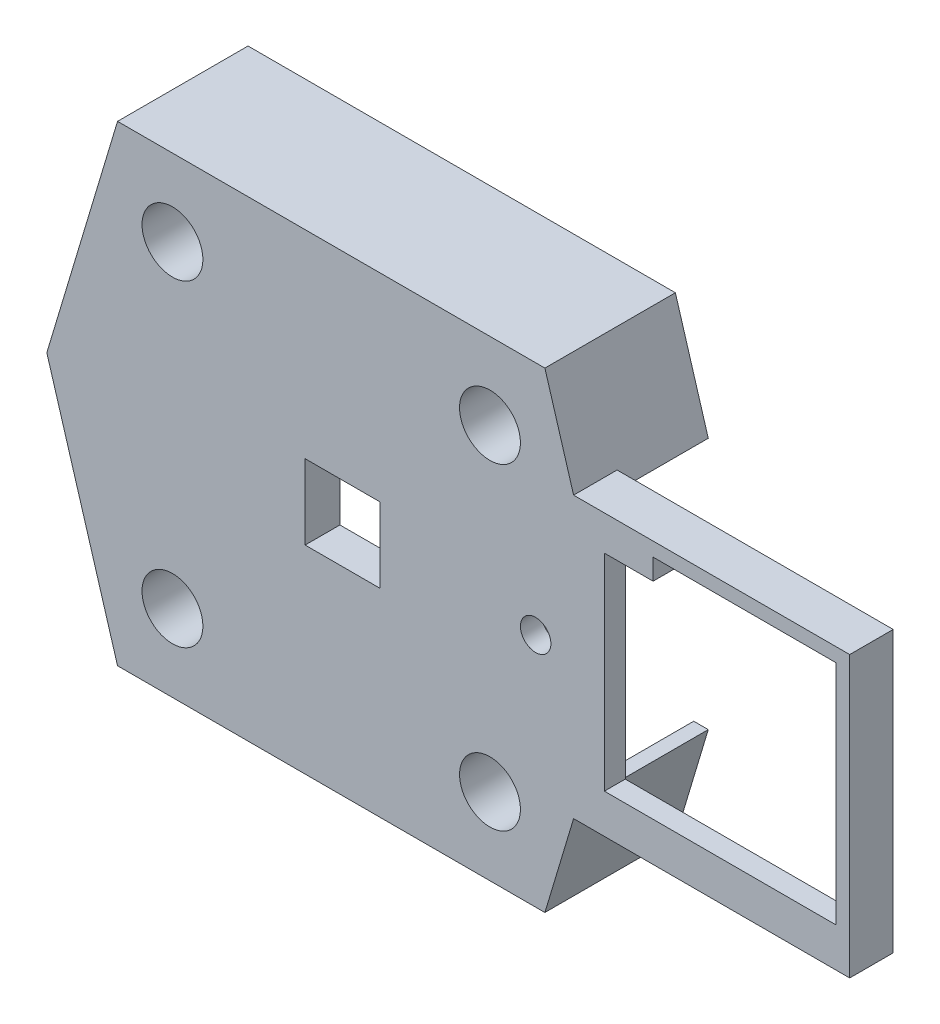
SolidWorks part; units mm, degrees
ref_plane "Front Plane" through (0, 0, 0) normal (0, 0, 1) x (1, 0, 0)
ref_plane "Top Plane" through (0, 0, 0) normal (0, 1, 0) x (1, 0, 0)
ref_plane "Right Plane" through (0, 0, 0) normal (1, 0, 0) x (0, 0, -1)
sketch "Sketch2" plane through (0, 0, 12) normal (0, 0, 1) x (1, 0, 0)
  line L10 (-24.5625, 27.1) -> (-32.6925, 0)
  line L11 (-32.6925, 0) -> (-24.5625, -27.1)
  line L12 (-24.5625, -27.1) -> (24.5625, -27.1)
  line L13 (24.5625, -27.1) -> (32.6925, 0)
  line L14 (32.6925, 0) -> (24.5625, 27.1)
  line L15 (24.5625, 27.1) -> (-24.5625, 27.1)
  line L16 (-23.372, 25.5) -> (-31.022, 0)
  line L17 (-31.022, 0) -> (-23.372, -25.5)
  line L18 (-23.372, -25.5) -> (23.372, -25.5)
  line L19 (23.372, -25.5) -> (31.022, 0)
  line L20 (31.022, 0) -> (23.372, 25.5)
  line L21 (23.372, 25.5) -> (-23.372, 25.5)
  line L22 (-23.372, 25.5) -> (-31.022, 0)
  line L23 (-31.022, 0) -> (-23.372, -25.5)
  line L24 (-23.372, -25.5) -> (23.372, -25.5)
  line L25 (23.372, -25.5) -> (31.022, 0)
  line L26 (31.022, 0) -> (23.372, 25.5)
  line L27 (23.372, 25.5) -> (-23.372, 25.5)
  dimension "D1" = 0.5
  dimension "D2" = 1.6
extrude "Boss-Extrude1" add sketch "Sketch2" along normal blind 10 and the other way blind 5
sketch "Sketch3" plane through (0, 0, 22) normal (0, 0, 1) x (1, 0, 0)
  line L0 (29.5, 16.1) -> (59.6, 16.1)
  line L1 (59.6, 16.1) -> (59.6, -16.1)
  line L2 (59.6, -16.1) -> (29.5, -16.1)
  line L3 (29.5, 16.1) -> (27.8625, 16.1)
  line L4 (27.8625, 16.1) -> (28.3425, 14.5)
  line L5 (29.5, -16.1) -> (27.8625, -16.1)
  line L6 (27.8625, -16.1) -> (28.3425, -14.5)
  line L12 (29.5, 14.5) -> (28.3425, 14.5)
  line L13 (32.6925, 0) -> (24.5625, 27.1) construction
  line L14 (29.5, -14.5) -> (28.3425, -14.5)
  line L15 (58, -14.5) -> (29.5, -14.5)
  line L16 (58, 14.5) -> (58, -14.5)
  line L17 (29.5, 14.5) -> (58, 14.5)
  line L18 (58, -14.5) -> (29.5, -14.5)
  line L19 (58, 14.5) -> (58, -14.5)
  line L20 (29.5, 14.5) -> (58, 14.5)
  line L21 (24.5625, -27.1) -> (32.6925, 0) construction
  dimension "D1" = 0.5
  dimension "D2" = 1.6
extrude "Boss-Extrude2" add sketch "Sketch3" against normal blind 5
sketch "Sketch4" plane through (0, 0, 7) normal (0, 0, -1) x (-1, 0, 0)
  line L0 (-28.3425, 14.5) -> (-26.672, 14.5)
  line L1 (-31.022, 0) -> (-23.372, 25.5) construction
  line L2 (-28.3425, -14.5) -> (-26.672, -14.5)
  line L3 (-23.372, -25.5) -> (-31.022, 0) construction
  line L6 (24.5625, 27.1) -> (-24.5625, 27.1)
  line L7 (-24.5625, 27.1) -> (-32.6925, 0)
  line L8 (-32.6925, 0) -> (-24.5625, -27.1)
  line L9 (-24.5625, -27.1) -> (24.5625, -27.1)
  line L10 (24.5625, -27.1) -> (32.6925, 0)
  line L11 (32.6925, 0) -> (24.5625, 27.1)
  line L12 (24.5625, 27.1) -> (-24.5625, 27.1)
  line L13 (-24.5625, 27.1) -> (-32.6925, 0)
  line L14 (-32.6925, 0) -> (-24.5625, -27.1)
  line L15 (-24.5625, -27.1) -> (24.5625, -27.1)
  line L16 (24.5625, -27.1) -> (32.6925, 0)
  line L17 (32.6925, 0) -> (24.5625, 27.1)
  line M7 (-31.022, 0) -> (-23.372, 25.5)
  line M12 (-23.372, -25.5) -> (-31.022, 0)
  line M14 (-24.5625, 27.1) -> (-32.6925, 0)
  line M15 (-32.6925, 0) -> (-24.5625, -27.1)
  dimension "D1" = 0
extrude "Cut-Extrude1" cut sketch "Sketch4" against normal through all contours L2 L0 M15 M12 M7 M14 region at (27.5072, 14.2038, 7)
sketch "Sketch5" plane through (0, 0, 22) normal (0, 0, 1) x (1, 0, 0)
  line L0 (-2.5, 3.8) -> (-2.5, -3.8) construction
  line L1 (-2.5, -3.8) -> (29.5, -3.8) construction
  line L2 (29.5, -3.8) -> (29.5, -14) construction
  line L3 (29.5, -14) -> (57.5, -14) construction
  line L4 (57.5, -14) -> (57.5, 14) construction
  line L5 (57.5, 14) -> (29.5, 14) construction
  line L6 (29.5, 14) -> (29.5, 3.8) construction
  line L7 (29.5, 3.8) -> (-2.5, 3.8) construction
  line L8 (24.5625, -27.1) -> (27.8625, -16.1) construction
  line L9 (27.8625, -16.1) -> (59.6, -16.1) construction
  line L10 (59.6, -16.1) -> (59.6, 16.1) construction
  line L11 (59.6, 16.1) -> (27.8625, 16.1) construction
  line L12 (27.8625, 16.1) -> (24.5625, 27.1) construction
  line L13 (24.5625, 27.1) -> (-24.5625, 27.1) construction
  line L14 (-24.5625, 27.1) -> (-32.6925, 0) construction
  line L15 (-32.6925, 0) -> (-24.5625, -27.1) construction
  line L16 (-24.5625, -27.1) -> (24.5625, -27.1) construction
  line L17 (-2.5, 3.8) -> (-2.5, -3.8)
  line L18 (-2.5, -3.8) -> (29.5, -3.8)
  line L19 (29.5, -3.8) -> (29.5, -14)
  line L20 (29.5, -14) -> (57.5, -14)
  line L21 (57.5, -14) -> (57.5, 14)
  line L22 (57.5, 14) -> (29.5, 14)
  line L23 (29.5, 14) -> (29.5, 3.8)
  line L24 (29.5, 3.8) -> (-2.5, 3.8)
  line L25 (24.5625, -27.1) -> (27.8625, -16.1)
  line L26 (27.8625, -16.1) -> (59.6, -16.1)
  line L27 (59.6, -16.1) -> (59.6, 16.1)
  line L28 (59.6, 16.1) -> (27.8625, 16.1)
  line L29 (27.8625, 16.1) -> (24.5625, 27.1)
  line L30 (24.5625, 27.1) -> (-24.5625, 27.1)
  line L31 (-24.5625, 27.1) -> (-32.6925, 0)
  line L32 (-32.6925, 0) -> (-24.5625, -27.1)
  line L33 (-24.5625, -27.1) -> (24.5625, -27.1)
  line L34 (29, 14) -> (29, 4.3)
  line L35 (29, 4.3) -> (-3, 4.3)
  line L36 (-3, 4.3) -> (-3, -4.3)
  line L37 (-3, -4.3) -> (29, -4.3)
  line L38 (29, -4.3) -> (29, -14)
  line L39 (29, 14) -> (29, 14.5)
  line L40 (26.672, 14.5) -> (58, 14.5) construction
  line L41 (29, -14) -> (29, -14.5)
  line L42 (58, -14.5) -> (26.672, -14.5) construction
  line L43 (27.4, 14) -> (27.4, 14.5)
  line L44 (27.4, 14) -> (27.4, 5.9)
  line L45 (27.4, 5.9) -> (-4.6, 5.9)
  line L46 (-4.6, 5.9) -> (-4.6, -5.9)
  line L47 (-4.6, -5.9) -> (27.4, -5.9)
  line L48 (27.4, -5.9) -> (27.4, -14)
  line L49 (27.4, -14) -> (27.4, -14.5)
  circle A0 centre (18.25, -18.25) radius 3.5 construction
  circle A1 centre (-18.25, -18.25) radius 3.5 construction
  circle A2 centre (-18.25, 18.25) radius 3.5 construction
  circle A3 centre (18.25, 18.25) radius 3.5 construction
  circle A4 centre (18.25, -18.25) radius 3.5
  circle A5 centre (-18.25, -18.25) radius 3.5
  circle A6 centre (-18.25, 18.25) radius 3.5
  circle A7 centre (18.25, 18.25) radius 3.5
  line M28 (26.672, 14.5) -> (58, 14.5)
  line M30 (58, -14.5) -> (26.672, -14.5)
  dimension "D1" = 0.5
  dimension "D2" = 1.6
extrude "Boss-Extrude3" add sketch "Sketch5" against normal blind 4 contours L48 L49 L41 L38 L37 L36 L35 L34 L39 L43 L44 L45 L46 L47 M30 M28 region at (28.5562, 9.15, 22)
sketch "Sketch7" plane through (0, 0, 22) normal (0, 0, 1) x (1, 0, 0)
  line L5 (37, 14.5) -> (37, 12.1)
  line L6 (29, 14.5) -> (58, 14.5) construction
  line L7 (37, 12.1) -> (31.4, 12.1)
  line L8 (31.4, 12.1) -> (31.4, -11.6)
  line L9 (31.4, -11.6) -> (58, -11.6)
  line L10 (58, 14.5) -> (58, -14.5) construction
  line L11 (5.6, 4.3) -> (5.6, -4.3)
  line L12 (29, 4.3) -> (-3, 4.3) construction
  line L13 (-3, -4.3) -> (29, -4.3) construction
  line L14 (29, 14.5) -> (29, 4.3) construction
  line L15 (-3, 4.3) -> (-3, -4.3) construction
  line L16 (29.5, -14) -> (57.5, -14) construction
  circle A0 centre (23.5, 0) radius 1.75 construction
  circle A1 centre (23.5, 0) radius 1.75
  line M29 (58, -14.5) -> (29, -14.5)
  line M30 (29, -14.5) -> (29, -4.3)
  line M31 (29, -4.3) -> (-3, -4.3)
  line M33 (-3, 4.3) -> (29, 4.3)
  line M34 (29, 4.3) -> (29, 14.5)
  line M35 (29, 14.5) -> (58, 14.5)
  line M36 (58, 14.5) -> (58, -14.5)
  dimension "D1" = 8.6
  dimension "D2" = 2.4
  dimension "D3" = 2.4
  dimension "D4" = 2.4
  dimension "D5" = 8
extrude "Boss-Extrude4" add sketch "Sketch7" against normal blind 2.4 contours L11 L9 L8 L7 L5 A1 M33 M31 M30 M29 M36 M35 M34 region at (26.3363, -2.3534, 22)
sketch "Sketch8" plane through (0, 0, 22) normal (0, 0, 1) x (1, 0, 0)
  circle A0 centre (-18.25, -18.25) radius 3.5 construction
  circle A1 centre (18.25, -18.25) radius 3.5 construction
  circle A2 centre (18.25, 18.25) radius 3.5 construction
  circle A3 centre (-18.25, 18.25) radius 3.5 construction
  circle A4 centre (-18.25, -18.25) radius 3.5
  circle A5 centre (18.25, -18.25) radius 3.5
  circle A6 centre (18.25, 18.25) radius 3.5
  circle A7 centre (-18.25, 18.25) radius 3.5
  line M11 (27.4, -5.9) -> (27.4, -14.5)
  line M12 (27.4, -14.5) -> (26.672, -14.5)
  line M13 (26.672, -14.5) -> (23.372, -25.5)
  line M14 (23.372, -25.5) -> (-23.372, -25.5)
  line M15 (-23.372, -25.5) -> (-31.022, 0)
  line M16 (-31.022, 0) -> (-23.372, 25.5)
  line M17 (-23.372, 25.5) -> (23.372, 25.5)
  line M18 (23.372, 25.5) -> (26.672, 14.5)
  line M19 (26.672, 14.5) -> (27.4, 14.5)
  line M20 (27.4, 14.5) -> (27.4, 5.9)
  line M21 (27.4, 5.9) -> (-4.6, 5.9)
  line M22 (-4.6, 5.9) -> (-4.6, -5.9)
  line M23 (-4.6, -5.9) -> (27.4, -5.9)
extrude "Boss-Extrude5" add sketch "Sketch8" against normal blind 1 contours A7 A6 A5 A4 M11 M23 M22 M21 M20 M19 M18 M17 M16 M15 M14 M13 M12 region at (26.6245, -10.2, 22)
sketch "Sketch9" plane through (0, 0, 21) normal (0, 0, -1) x (-1, 0, 0)
  circle A0 centre (-18.25, -18.25) radius 3.5 construction
  circle A1 centre (18.25, -18.25) radius 3.5 construction
  circle A2 centre (18.25, 18.25) radius 3.5 construction
  circle A3 centre (-18.25, 18.25) radius 3.5 construction
  circle A4 centre (-18.25, -18.25) radius 3.5
  circle A5 centre (18.25, -18.25) radius 3.5
  circle A6 centre (18.25, 18.25) radius 3.5
  circle A7 centre (-18.25, 18.25) radius 3.5
  circle A8 centre (-18.25, 18.25) radius 5.1
  circle A9 centre (18.25, 18.25) radius 5.1
  circle A10 centre (18.25, -18.25) radius 5.1
  circle A11 centre (-18.25, -18.25) radius 5.1
  dimension "D1" = 1.6
extrude "Boss-Extrude6" add sketch "Sketch9" along normal blind 9
